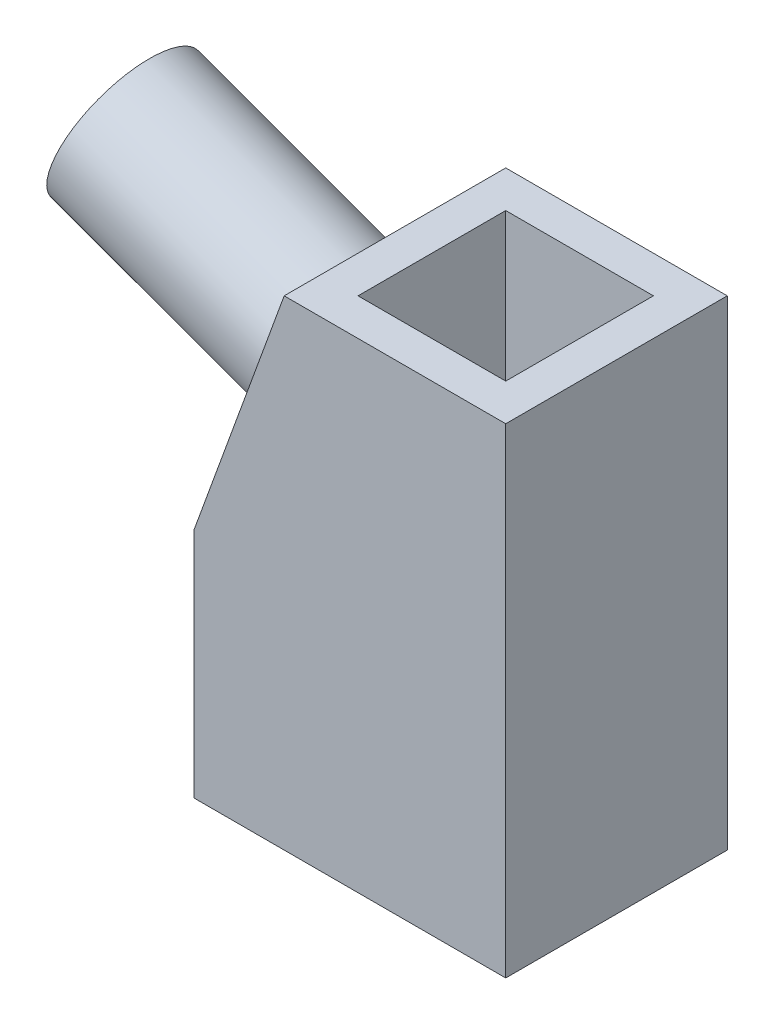
SolidWorks part; units mm, degrees
ref_plane "Front Plane" through (0, 0, 0) normal (0, 0, 1) x (1, 0, 0)
ref_plane "Top Plane" through (0, 0, 0) normal (0, 1, 0) x (1, 0, 0)
ref_plane "Right Plane" through (0, 0, 0) normal (1, 0, 0) x (0, 0, -1)
sketch "Sketch1" plane through (0, 0, 0) normal (0, 1, 0) x (1, 0, 0)
  line L1 (0, 0) -> (53.594, 0)
  line L2 (0, 0) -> (0, 38.1)
  line L3 (0, 38.1) -> (53.594, 38.1)
  line L4 (53.594, 0) -> (53.594, 38.1)
  dimension "D1" = 53.594
  dimension "D2" = 38.1
extrude "Boss-Extrude1" add sketch "Sketch1" along normal blind 82.55
sketch "Sketch4" plane through (0, 0, 0) normal (0, 0, 1) x (1, 0, 0)
  line L0 (53.594, 82.55) -> (15.494, 82.55)
  line L1 (0, 82.55) -> (53.594, 82.55) construction
  line L2 (15.494, 82.55) -> (-13.2573, 3.5565)
  line L3 (0, 82.55) -> (0, 39.9806)
  line L4 (0, 82.55) -> (0, 0) construction
  line L5 (15.494, 82.55) -> (0, 82.55)
  line M5 (53.594, 82.55) -> (0, 82.55)
  line M6 (0, 82.55) -> (0, 0)
  dimension "D1" = 38.1
  dimension "D2" = 110
extrude "Cut-Extrude1" cut sketch "Sketch4" against normal through all contours L2 M5 M6 region at (5.1647, 68.3602, 0)
sketch "Sketch5" plane through (0, 82.55, 0) normal (0, 1, 0) x (1, 0, 0)
  line L0 (53.594, 0) -> (53.594, 38.1) construction
  line L1 (21.844, 31.75) -> (47.244, 31.75)
  line L2 (21.844, 31.75) -> (21.844, 6.35)
  line L3 (21.844, 6.35) -> (47.244, 6.35)
  line L4 (47.244, 31.75) -> (47.244, 6.35)
  line L5 (53.594, 38.1) -> (15.494, 38.1) construction
  dimension "D1" = 25.4
  dimension "D2" = 25.4
  dimension "D3" = 6.35
  dimension "D4" = 6.35
extrude "Cut-Extrude2" cut sketch "Sketch5" against normal through all
sketch "Sketch6" plane through (-12.8495, 4.6768, 0) normal (-0.9397, 0.342, 0) x (0, 0, 1)
  line L3 (-38.1, 82.8709) -> (-38.1, 37.5695)
  line L4 (-38.1, 37.5695) -> (0, 37.5695)
  circle A0 centre (-19.05, 60.2202) radius 12.6365
  point P2 (-38.1, 60.2202)
  point P3 (-19.05, 37.5695)
  dimension "D2" = 25.273
extrude "Boss-Extrude2" add sketch "Sketch6" along normal blind 41.275 contours A0 region at (7.747, 61.2653, -19.05)
ref_axis "Axis1" through (-26.5017, 73.7308, -19.05) along (0.9397, -0.342, 0)
